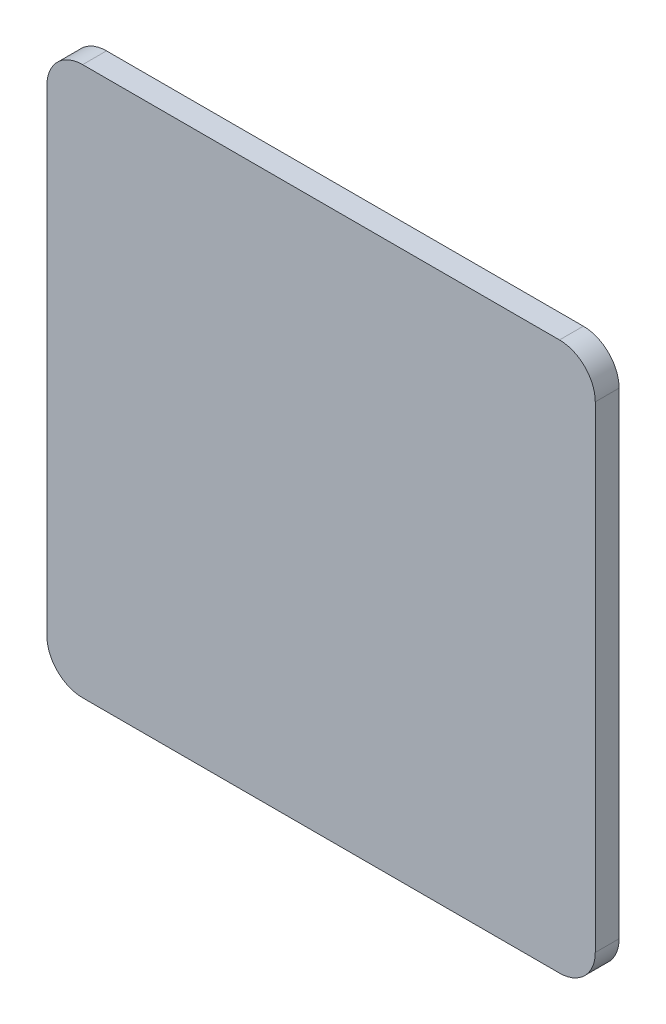
SolidWorks part; units mm, degrees
material "Beech"
ref_plane "Front Plane" through (0, 0, 0) normal (0, 0, 1) x (1, 0, 0)
ref_plane "Top Plane" through (0, 0, 0) normal (0, 1, 0) x (1, 0, 0)
ref_plane "Right Plane" through (0, 0, 0) normal (1, 0, 0) x (0, 0, -1)
sketch "Sketch1" plane through (0, 0, 0) normal (0, 0, 1) x (1, 0, 0)
  line L1 (58.42, 58.42) -> (-58.42, 58.42)
  line L2 (58.42, 58.42) -> (58.42, -58.42)
  line L3 (58.42, -58.42) -> (-58.42, -58.42)
  line L4 (-58.42, 58.42) -> (-58.42, -58.42)
  line L5 (58.42, 58.42) -> (-58.42, -58.42) construction
  line L6 (58.42, -58.42) -> (-58.42, 58.42) construction
  point P0 (0, 0)
  dimension "D1" = 116.84
  dimension "D2" = 116.84
extrude "Boss-Extrude1" add sketch "Sketch1" along normal blind 5.08
fillet "Fillet1" radius 7.62 4 edges at (-58.42, -58.42, 2.54) (58.42, -58.42, 2.54) (58.42, 58.42, 2.54) (-58.42, 58.42, 2.54)
